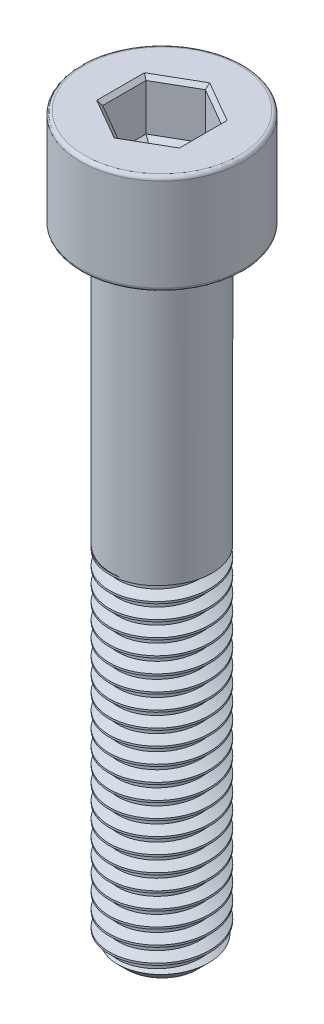
SolidWorks part; units mm, degrees
material "AISI Type A2 Tool Steel"
ref_plane "Front Plane" through (0, 0, 0) normal (0, 0, 1) x (1, 0, 0)
ref_plane "Top Plane" through (0, 0, 0) normal (0, 1, 0) x (1, 0, 0)
ref_plane "Right Plane" through (0, 0, 0) normal (1, 0, 0) x (0, 0, -1)
sketch "Sketch1" plane through (0, 0, 0) normal (0, 1, 0) x (1, 0, 0)
  circle A0 centre (0, 0) radius 4
  dimension "D1" = 8
extrude "Boss-Extrude1" add sketch "Sketch1" along normal blind 28
thread "Thread1" pitch 1.25 method cut profile "Thread Profile1" start angle 0, offset 2, length 0, pitch 1.25, diameter 8
ref_plane "Plane1" through (-4, 30, 0) normal (0, 0, 1) x (-1, 0, 0)
sketch "Thread Profile1" plane through (-4, 30, 0) normal (0, 0, 1) x (-1, 0, 0)
  line L0 (0, 0) -> (0, 1.25) construction
  line L11 (0, 0) -> (0, 1.0937)
  line L12 (0, 1.0937) -> (-0.6766, 0.7031)
  line L13 (-0.6766, 0.7031) -> (-0.6766, 0.3906)
  line L15 (-0.6766, 0.3906) -> (0, 0)
  line L17 (-0.6766, 0.5469) -> (0, 0.5469) construction
  point P2 (0, 0)
  dimension "Pitch" = 1.25
  dimension "Profile_Angle" = 60
  dimension "Profile_Land" = 0.3125
  dimension "Profile_Height" = 0.6766
sketch "Sketch2" plane through (0, 28, 0) normal (0, 1, 0) x (1, 0, 0)
  circle A0 centre (0, 0) radius 4
  dimension "D1" = 8
extrude "Boss-Extrude2" add sketch "Sketch2" along normal blind 22
sketch "Sketch5" plane through (0, 50, 0) normal (0, 1, 0) x (1, 0, 0)
  circle A0 centre (0, 0) radius 6.5
  dimension "D1" = 13
extrude "Boss-Extrude3" add sketch "Sketch5" along normal blind 8
sketch "Sketch6" plane through (0, 0, 0) normal (0, 0, 1) x (1, 0, 0)
  line L0 (0, 0) -> (0, 0.7245) construction
  line L1 (0, 0) -> (4.01, 0) construction
  line L2 (4.01, 0) -> (4.01, 1.2)
  line L3 (4.01, 1.2) -> (2.81, 0)
  line L4 (2.81, 0) -> (4.01, 0)
  dimension "D1" = 1.2
  dimension "D2" = 45
  dimension "D3" = 4.01
revolve "Cut-Revolve1" cut sketch "Sketch6" angle 360 about L0
fillet "Fillet1" radius 0.3 2 edges at (0, 50, 6.5) (0, 58, 6.5)
sketch "Sketch7" plane through (0, 58, 0) normal (0, 1, 0) x (1, 0, 0)
  line L1 (0, 3.4641) -> (-3, 1.7321)
  line L2 (-3, 1.7321) -> (-3, -1.7321)
  line L3 (-3, -1.7321) -> (0, -3.4641)
  line L4 (0, -3.4641) -> (3, -1.7321)
  line L5 (3, -1.7321) -> (3, 1.7321)
  line L6 (3, 1.7321) -> (0, 3.4641)
  circle A0 centre (0, 0) radius 3 construction
  dimension "D1" = 6
extrude "Cut-Extrude1" cut sketch "Sketch7" against normal blind 4
chamfer "Chamfer1" distance 0.3 angle 45 6 edges at (-3, 58, 0) (-1.5, 58, 2.5981) (1.5, 58, 2.5981) (3, 58, 0) (1.5, 58, -2.5981) (-1.5, 58, -2.5981)
sketch "Sketch8" plane through (0, 54, 0) normal (0, 1, 0) x (1, 0, 0)
  line L1 (0, 3.4641) -> (-3, 1.7321)
  line L2 (-3, 1.7321) -> (-3, -1.7321)
  line L3 (-3, -1.7321) -> (0, -3.4641)
  line L4 (0, -3.4641) -> (3, -1.7321)
  line L5 (3, -1.7321) -> (3, 1.7321)
  line L6 (3, 1.7321) -> (0, 3.4641)
  circle A0 centre (0, 0) radius 3 construction
extrude "Cut-Extrude2" cut sketch "Sketch8" against normal blind 0.4 draft 60
